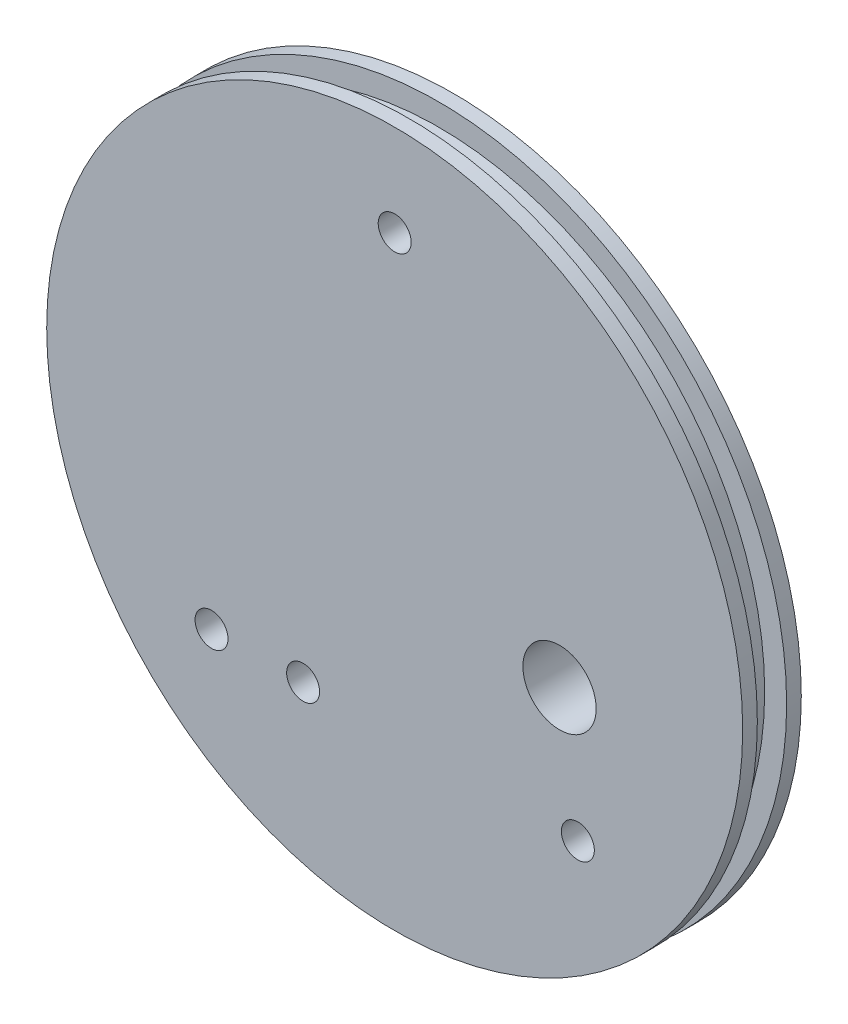
SolidWorks part; units mm, degrees
ref_plane "Front Plane" through (0, 0, 0) normal (0, 0, 1) x (1, 0, 0)
ref_plane "Top Plane" through (0, 0, 0) normal (0, 1, 0) x (1, 0, 0)
ref_plane "Right Plane" through (0, 0, 0) normal (1, 0, 0) x (0, 0, -1)
sketch "Sketch2" plane through (0, 0, 0) normal (0, 0, 1) x (1, 0, 0)
  circle A0 centre (0, 0) radius 89
  circle A1 centre (0, 0) radius 95
  dimension "D1" = 178
  dimension "D2" = 190
extrude "Boss-Extrude1" add sketch "Sketch2" along normal blind 8 and the other way blind 8 contours A1 A0 | A0 region at (-92.313, 0, 0)
extrude "Cut-Extrude1" cut sketch "Sketch2<5>" against normal blind 4 and the other way blind 4
sketch "Sketch2<5>" plane through (0, 0, 0) normal (0, 0, 1) x (1, 0, 0) same geometry as "Sketch2"
sketch "Sketch3" plane through (0, 0, 8) normal (0, 0, 1) x (1, 0, 0)
  line L0 (0, 33.75) -> (0, -33.75) construction
  line L1 (41.5, 33.75) -> (-78.5, 33.75)
  line L2 (41.5, 33.75) -> (41.5, -33.75)
  line L3 (41.5, -33.75) -> (-78.5, -33.75) construction
  line L4 (-78.5, 33.75) -> (-78.5, -33.75) construction
  line L5 (31, 33.75) -> (31, -33.75) construction
  line L6 (41.5, 0) -> (-78.5, 0) construction
  line L7 (-78.5, 28.75) -> (-43.5, 28.75)
  line L8 (-43.5, 28.75) -> (-43.5, -33.75)
  line L9 (-78.5, 33.75) -> (-78.5, 28.75)
  line L10 (-43.5, -33.75) -> (41.5, -33.75)
  circle A0 centre (0, 0) radius 31
  circle A1 centre (0, 0) radius 33.75
  point P9 (0, 0)
  dimension "D3" = 62
  dimension "D7" = 67.5
  dimension "D1" = 10.5
  dimension "D2" = 120
  dimension "D4" = 67.5
  dimension "D5" = 5
  dimension "D6" = 35
sketch "Sketch4" plane through (0, 0, -8) normal (0, 0, 1) x (1, 0, 0)
  line L0 (0, 33.75) -> (0, -33.75) construction
  line L1 (41.5, 33.75) -> (-78.5, 33.75)
  line L2 (41.5, 33.75) -> (41.5, -33.75)
  line L3 (41.5, -33.75) -> (-78.5, -33.75) construction
  line L4 (-78.5, 33.75) -> (-78.5, -33.75) construction
  line L5 (31, 33.75) -> (31, -33.75) construction
  line L6 (41.5, 0) -> (-78.5, 0) construction
  line L7 (-78.5, 28.75) -> (-43.5, 28.75)
  line L8 (-43.5, 28.75) -> (-43.5, -33.75)
  line L9 (-78.5, 33.75) -> (-78.5, 28.75)
  line L10 (-43.5, -33.75) -> (41.5, -33.75)
  circle A0 centre (0, 0) radius 31
  point P9 (0, 0)
  dimension "D3" = 62
  dimension "D1" = 10.5
  dimension "D2" = 120
  dimension "D4" = 67.5
  dimension "D5" = 5
  dimension "D6" = 35
ref_plane "Plane1" through (0, -33.75, 0) normal (0, 1, 0) x (1, 0, 0)
sketch "Sketch7" plane through (0, 0, 8) normal (0, 0, 1) x (1, 0, 0)
  line L0 (0, -33.75) -> (0, -48.75) construction
  line L1 (-50, -48.75) -> (50, -48.75) construction
  line L2 (0, -48.75) -> (20, -48.75) construction
  line L3 (0, -48.75) -> (3.6347, -48.75) construction
  circle A0 centre (-50, -48.75) radius 4.5
  circle A1 centre (50, -48.75) radius 4.5
  circle A5 centre (-25, -48.75) radius 4.5
  point P7 (0, -48.75)
  dimension "D3" = 9
  dimension "D4" = 9
  dimension "D7" = 25
  dimension "D6" = 9
  dimension "D1" = 100
  dimension "D2" = 15
extrude "Cut-Extrude2" cut sketch "Sketch7" against normal blind 167
sketch "Sketch10" plane through (0, 0, -8) normal (0, 0, -1) x (-1, 0, 0)
  line L0 (0, 0) -> (0, 70) construction
  circle A0 centre (0, 70) radius 4.5
  circle A1 centre (0, 70) radius 6
  dimension "D2" = 9
  dimension "D3" = 12
  dimension "D1" = 70
extrude "Cut-Extrude4" cut sketch "Sketch10" against normal blind 60 and the other way blind 112 contours A0 region at (0, 70, -8)
sketch "Sketch11" plane through (0, 0, -8) normal (0, 0, -1) x (-1, 0, 0)
  line L0 (0, 0) -> (0, -15) construction
  line L1 (0, -15) -> (-45, -15) construction
  circle A0 centre (-45, -15) radius 10
  dimension "D3" = 20
  dimension "D1" = 15
  dimension "D2" = 45
extrude "Cut-Extrude5" cut sketch "Sketch11" against normal blind 60 contours A0
